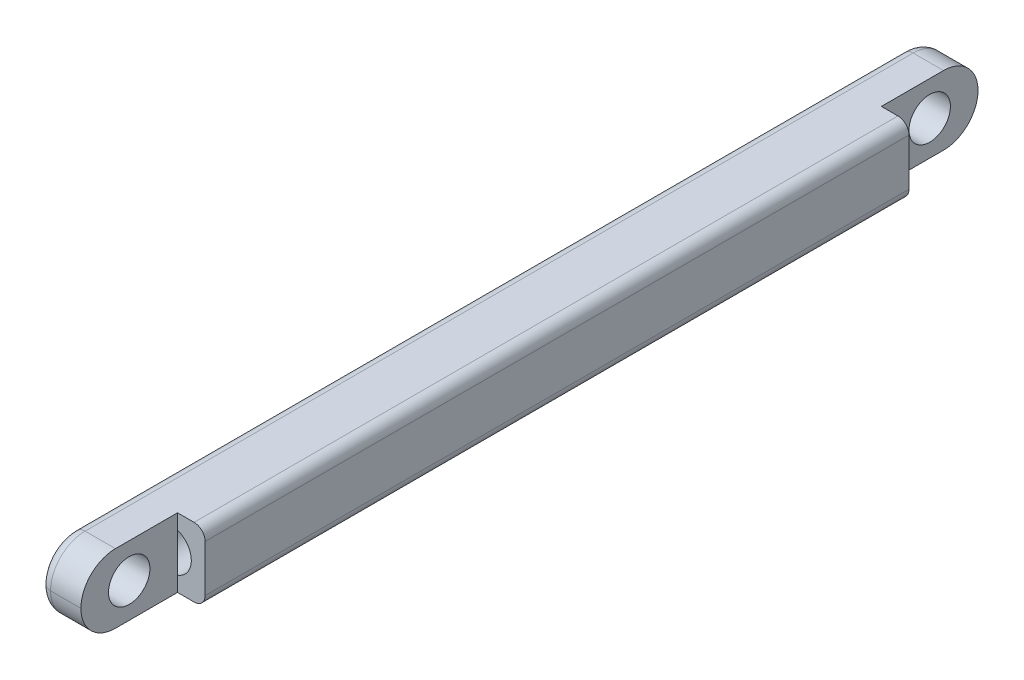
SolidWorks part; units mm, degrees
ref_plane "前视基准面" through (0, 0, 0) normal (0, 0, 1) x (1, 0, 0)
ref_plane "上视基准面" through (0, 0, 0) normal (0, 1, 0) x (1, 0, 0)
ref_plane "右视基准面" through (0, 0, 0) normal (1, 0, 0) x (0, 0, -1)
sketch "草图1" plane through (0, 0, 0) normal (0, 0, 1) x (1, 0, 0)
  line L1 (-2.5, 2.5) -> (2.5, 2.5)
  line L2 (-2.5, 2.5) -> (-2.5, -2.5)
  line L3 (-2.5, -2.5) -> (2.5, -2.5)
  line L4 (2.5, 2.5) -> (2.5, -2.5)
  line L5 (-2.5, 2.5) -> (2.5, -2.5) construction
  line L6 (-2.5, -2.5) -> (2.5, 2.5) construction
  point P0 (0, 0)
  dimension "D1" = 5
  dimension "D2" = 5
extrude "凸台-拉伸1" add sketch "草图1" along normal blind 51
sketch "草图2" plane through (0, 0, 51) normal (0, 0, 1) x (1, 0, 0)
  circle A0 centre (0, 0) radius 1.5
  dimension "D1" = 3
extrude "切除-拉伸1" cut sketch "草图2" against normal through all
sketch "草图3" plane through (0, 0, 51) normal (0, 0, 1) x (1, 0, 0)
  line L0 (-2.5, 2.5) -> (0.5, 2.5)
  line L1 (2.5, 2.5) -> (-2.5, 2.5) construction
  line L2 (0.5, 2.5) -> (0.5, -2.5)
  line L3 (-2.5, -2.5) -> (2.5, -2.5) construction
  line L4 (0.5, -2.5) -> (-2.5, -2.5)
  line L5 (-2.5, -2.5) -> (-2.5, 2.5)
  dimension "D1" = 3
extrude "凸台-拉伸2" add sketch "草图3" along normal blind 7
fillet "圆角1" radius 2.5 2 edges at (-1, -2.5, 58) (-1, 2.5, 58)
sketch "草图4" plane through (-2.5, 0, 0) normal (-1, 0, 0) x (0, 0, 1)
  line L0 (54.5, 0) -> (58, 0) construction
  arc A0 (55.5, -2.5) -> (58, 0) centre (55.5, 0) ccw construction
  circle A1 centre (54.5, 0) radius 1.5
  dimension "D2" = 3
  dimension "D1" = 3.5
extrude "切除-拉伸2" cut sketch "草图4" against normal through all
sketch "草图5" plane through (0, 0, 0) normal (0, 0, -1) x (-1, 0, 0)
  line L0 (2.5, 2.5) -> (-0.5, 2.5)
  line L1 (-2.5, 2.5) -> (2.5, 2.5) construction
  line L2 (-0.5, 2.5) -> (-0.5, -2.5)
  line L3 (-0.5, -2.5) -> (2.5, -2.5)
  line L4 (2.5, -2.5) -> (2.5, 2.5)
  dimension "D1" = 3
extrude "凸台-拉伸3" add sketch "草图5" along normal blind 7
fillet "圆角2" radius 2.5 2 edges at (-1, -2.5, -7) (-1, 2.5, -7)
sketch "草图6" plane through (0.5, 0, 0) normal (1, 0, 0) x (0, 0, -1)
  line L0 (3.5, 0) -> (7, 0) construction
  circle A0 centre (3.5, 0) radius 1.5
  dimension "D2" = 3
  dimension "D1" = 3.5
extrude "切除-拉伸3" cut sketch "草图6" against normal through all
fillet "圆角3" radius 0.8 8 edges at (-2.5, 1.7678, 57.2678) (-2.5, -1.7678, 57.2678) (-2.5, -2.5, 25.5) (-2.5, -1.7678, -6.2678) (-2.5, 1.7678, -6.2678) (-2.5, 2.5, 25.5) (2.5, -2.5, 25.5) (2.5, 2.5, 25.5)
